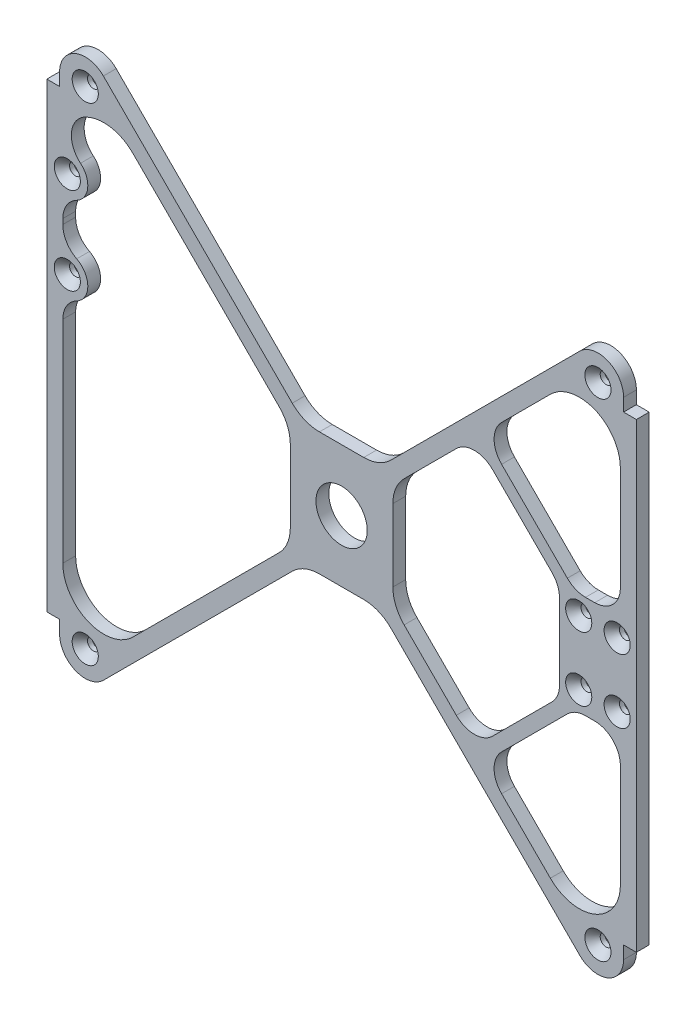
SolidWorks part; units mm, degrees
material "6061-T6 (SS)"
ref_plane "Front Plane" through (0, 0, 0) normal (0, 0, 1) x (1, 0, 0)
ref_plane "Top Plane" through (0, 0, 0) normal (0, 1, 0) x (1, 0, 0)
ref_plane "Right Plane" through (0, 0, 0) normal (1, 0, 0) x (0, 0, -1)
sketch "Sketch1" plane through (0, 0, 0) normal (0, 0, 1) x (1, 0, 0)
  line L0 (0, 0) -> (0, 73.025) construction
  line L1 (0, 0) -> (73.025, 0) construction
  line L2 (73.025, 73.025) -> (73.025, 0) construction
  line L3 (9.4347, 15.24) -> (0, 15.24)
  line L4 (12.7, 12.8926) -> (12.7, 0)
  line L5 (9.4347, 15.24) -> (59.0099, 64.8151)
  line L6 (12.7, 12.8926) -> (51.712, 51.9046)
  line L7 (69.0563, 44.7204) -> (69.0563, 0)
  line L8 (0, 73.025) -> (73.025, 73.025) construction
  line L9 (73.025, 57.15) -> (73.025, 0)
  line L10 (69.85, 60.325) -> (69.85, 57.15)
  line L11 (0, 0) -> (12.7, 0)
  line L12 (0, 15.24) -> (0, 0)
  line L13 (69.0563, 0) -> (73.025, 0)
  line L26 (69.85, 57.15) -> (73.025, 57.15)
  arc A1 (69.85, 60.325) -> (59.0099, 64.8151) centre (63.5, 60.325) ccw
  arc A2 (51.712, 51.9046) -> (69.0563, 44.7204) centre (58.8963, 44.7204) cw
  point P51 (12, 0)
  dimension "D11" = 6.35
  dimension "D5" = 10.16
  dimension "D3" = 12.7
  dimension "D6" = 3.9688
  dimension "D7" = 73.025
  dimension "D10" = 12.7
  dimension "D2" = 73.025
  dimension "D4" = 15.24
  dimension "D9" = 9.525
  dimension "D12" = 135
  dimension "D14" = 3.9688
  dimension "D8" = 15.875
extrude "Boss-Extrude1" add sketch "Sketch1" along normal blind 3.175
sketch "LOCATES-SCREW" plane through (0, 0, 3.175) normal (0, 0, 1) x (1, 0, 0)
  point P0 (63.5, 60.325)
hole_wizard "CSK for #4 Flat Head Machine Screw1" positions "Sketch10" profile "Sketch11" countersink size "#4" standard "ANSI Inch" end condition through all
sketch "Sketch10" plane through (0, 0, 3.175) normal (0, 0, 1) x (1, 0, 0)
  point P0 (63.5, 60.325)
sketch "Sketch11" plane through (63.5, 60.325, 3.175) normal (1, 0, 0) x (0, -1, 0)
  line L0 (0, 0) -> (0, 3.175)
  line L1 (0, 3.175) -> (1.4732, 3.175)
  line L2 (1.4732, 3.175) -> (1.4732, 2.0307)
  line L3 (1.4732, 2.0307) -> (3.2385, 0)
  line L5 (3.2385, 0) -> (0, 0)
  line L6 (-1.4732, 2.0307) -> (-3.2385, 0) construction
  line L11 (0, -6.35) -> (0, 107.95) construction
  dimension "Thru Hole Dia." = 2.9464
  dimension "Thru Hole Depth" = 3.175
  dimension "Near C'Sink Dia." = 6.477
  dimension "Near C'Sink Angle" = 82
mirror "Mirror1" about plane through (0, 0, 0) normal (0, 1, 0) of "CSK for #4 Flat Head Machine Screw1", "Boss-Extrude1"
mirror "Mirror2" about plane through (0, 0, 0) normal (1, 0, 0) of "Mirror1"
chamfer "COUNTERSINK" [suppressed] distance 1.27 angle 45
fillet "INTERNAL-SHARPS" radius 9.525 8 edges at (9.4347, 15.24, 1.5875) (-9.4347, 15.24, 1.5875) (12.7, -12.8926, 1.5875) (12.7, 12.8926, 1.5875) (9.4347, -15.24, 1.5875) (-9.4347, -15.24, 1.5875) (-12.7, -12.8926, 1.5875) (-12.7, 12.8926, 1.5875)
sketch "Sketch5" plane through (0, 0, 0) normal (0, 0, 1) x (1, 0, 0)
  line L0 (15.4898, 15.6824) -> (51.712, 51.9046) construction
  line L1 (69.0563, 44.7204) -> (69.0563, -44.7204) construction
  line L2 (73.025, 0) -> (54, 0) construction
  line L3 (69.0563, 12.7) -> (57.785, 12.7)
  line L4 (53.975, -12.0199) -> (53.975, 12.0199)
  line L5 (73.025, -57.15) -> (73.025, 57.15) construction
  line L6 (32.9011, 33.0937) -> (35.1462, 35.3388)
  line L7 (53.975, 12.0199) -> (32.9011, 33.0937)
  line L8 (57.785, 12.7) -> (35.1462, 35.3388)
  line L9 (69.0563, 12.7) -> (69.0563, -12.7)
  line L10 (69.0563, -12.7) -> (57.785, -12.7)
  line L11 (57.785, -12.7) -> (35.1462, -35.3388)
  line L12 (53.975, -12.0199) -> (32.9011, -33.0937)
  line L13 (32.9011, -33.0937) -> (35.1462, -35.3388)
  circle A0 centre (58.7375, 7.9375) radius 1.65 construction
  circle A1 centre (68.2625, 7.9375) radius 1.65 construction
  circle A2 centre (68.2625, -7.9375) radius 1.65 construction
  circle A3 centre (58.7375, -7.9375) radius 1.65 construction
  dimension "D1" = 3.3
  dimension "D2" = 12.7
  dimension "D3" = 15.24
  dimension "D4" = 9.525
  dimension "D5" = 15.875
  dimension "D6" = 4.7625
  dimension "D7" = 3.175
  dimension "D8" = 19.05
extrude "BRAKE-MOUNT" add sketch "Sketch5" along normal blind 3.175
sketch "PROJECTED-FROM-SKETCH-5" plane through (0, 0, 3.175) normal (0, 0, 1) x (1, 0, 0)
  circle A0 centre (58.7375, 7.9375) radius 1.65 construction
  circle A1 centre (58.7375, 7.9375) radius 1.65
  circle A2 centre (68.2625, 7.9375) radius 1.65 construction
  circle A3 centre (68.2625, -7.9375) radius 1.65 construction
  circle A4 centre (58.7375, -7.9375) radius 1.65 construction
  circle A5 centre (68.2625, 7.9375) radius 1.65
  circle A6 centre (68.2625, -7.9375) radius 1.65
  circle A7 centre (58.7375, -7.9375) radius 1.65
extrude "Cut-Extrude1" [suppressed] cut sketch "PROJECTED-FROM-SKETCH-5" against normal through all
fillet "Fillet1" radius 6.35 10 edges at (69.0563, -12.7, 1.5875) (57.785, -12.7, 1.5875) (35.1462, -35.3388, 1.5875) (32.9011, -33.0937, 1.5875) (53.975, -12.0199, 1.5875) (53.975, 12.0199, 1.5875) (32.9011, 33.0937, 1.5875) (35.1462, 35.3388, 1.5875) (57.785, 12.7, 1.5875) (69.0563, 12.7, 1.5875)
sketch "Sketch6" plane through (0, 0, 0) normal (0, 0, -1) x (-1, 0, 0)
  circle A0 centre (0, 0) radius 6.35
  dimension "D1" = 12.7
extrude "BEARING-POCKET" cut sketch "Sketch6" against normal up to next
sketch "Sketch13" plane through (0, 0, 0) normal (0, 0, 1) x (1, 0, 0)
  line L0 (-73.025, 57.15) -> (-73.025, -57.15) construction
  line L1 (-73.025, 44.45) -> (-73.025, 12.7)
  line L2 (-73.025, 12.7) -> (-67.945, 12.7)
  line L3 (-73.025, 44.45) -> (-67.945, 44.45)
  line L4 (-69.0563, -44.7204) -> (-69.0563, 44.7204) construction
  line L6 (-69.0563, 22.737) -> (-69.0563, 34.413)
  arc A0 (-69.0563, 34.413) -> (-67.945, 44.45) centre (-67.945, 39.37) ccw
  arc A1 (-67.945, 12.7) -> (-69.0563, 22.737) centre (-67.945, 17.78) ccw
  circle A3 centre (-63.5, 60.325) radius 1.4732 construction
  point P10 (-69.0563, 28.575)
  dimension "D5" = 5.08
  dimension "D1" = 31.75
  dimension "D2" = 21.59
  dimension "D3" = 31.75
extrude "IMU-MOUNTING" add sketch "Sketch13" along normal blind 3.175
hole_wizard "IMU-MOUNTING-HOLES" positions "Sketch14" profile "Sketch15" countersink size "#4" standard "ANSI Inch" end condition through all
sketch "Sketch14" plane through (0, 0, 3.175) normal (0, 0, 1) x (1, 0, 0)
  arc A0 (-67.945, 12.7) -> (-69.0563, 22.737) centre (-67.945, 17.78) ccw construction
  point P1 (-67.945, 17.78)
  point P7 (-67.945, 39.37)
  dimension "D1" = 21.59
sketch "Sketch15" plane through (-67.945, 17.78, 3.175) normal (1, 0, 0) x (0, -1, 0)
  line L0 (0, 0) -> (0, 3.175)
  line L1 (0, 3.175) -> (1.4732, 3.175)
  line L2 (1.4732, 3.175) -> (1.4732, 2.0307)
  line L3 (1.4732, 2.0307) -> (3.2385, 0)
  line L5 (3.2385, 0) -> (0, 0)
  line L6 (-1.4732, 2.0307) -> (-3.2385, 0) construction
  line L11 (0, -6.35) -> (0, 107.95) construction
  dimension "Thru Hole Dia." = 2.9464
  dimension "Thru Hole Depth" = 3.175
  dimension "Near C'Sink Dia." = 6.477
  dimension "Near C'Sink Angle" = 82
fillet "Fillet4" radius 6.35 4 edges at (-69.0563, 44.45, 1.5875) (-69.0563, 12.7, 1.5875) (-69.0563, 22.737, 1.5875) (-69.0563, 34.413, 1.5875)
hole_wizard "CSK for #4 Flat Head Machine Screw2" positions "3DSketch2" profile "Sketch17" countersink size "#4" standard "ANSI Inch" end condition through all
sketch3d "3DSketch2"
  point P0 (58.7375, -7.9375, 3.175)
  point P3 (58.7375, 7.9375, 3.175)
  point P6 (68.2625, 7.9375, 3.175)
  point P9 (68.2625, -7.9375, 3.175)
sketch "Sketch17" plane through (58.7375, -7.9375, 3.175) normal (1, 0, 0) x (0, -1, 0)
  line L0 (0, 0) -> (0, 3.175)
  line L1 (0, 3.175) -> (1.4732, 3.175)
  line L2 (1.4732, 3.175) -> (1.4732, 2.0307)
  line L3 (1.4732, 2.0307) -> (3.2385, 0)
  line L5 (3.2385, 0) -> (0, 0)
  line L6 (-1.4732, 2.0307) -> (-3.2385, 0) construction
  line L11 (0, -6.35) -> (0, 107.95) construction
  dimension "Thru Hole Dia." = 2.9464
  dimension "Thru Hole Depth" = 3.175
  dimension "Near C'Sink Dia." = 6.477
  dimension "Near C'Sink Angle" = 82
equation "\"D14@Sketch1\"=\"D6@Sketch1\""
